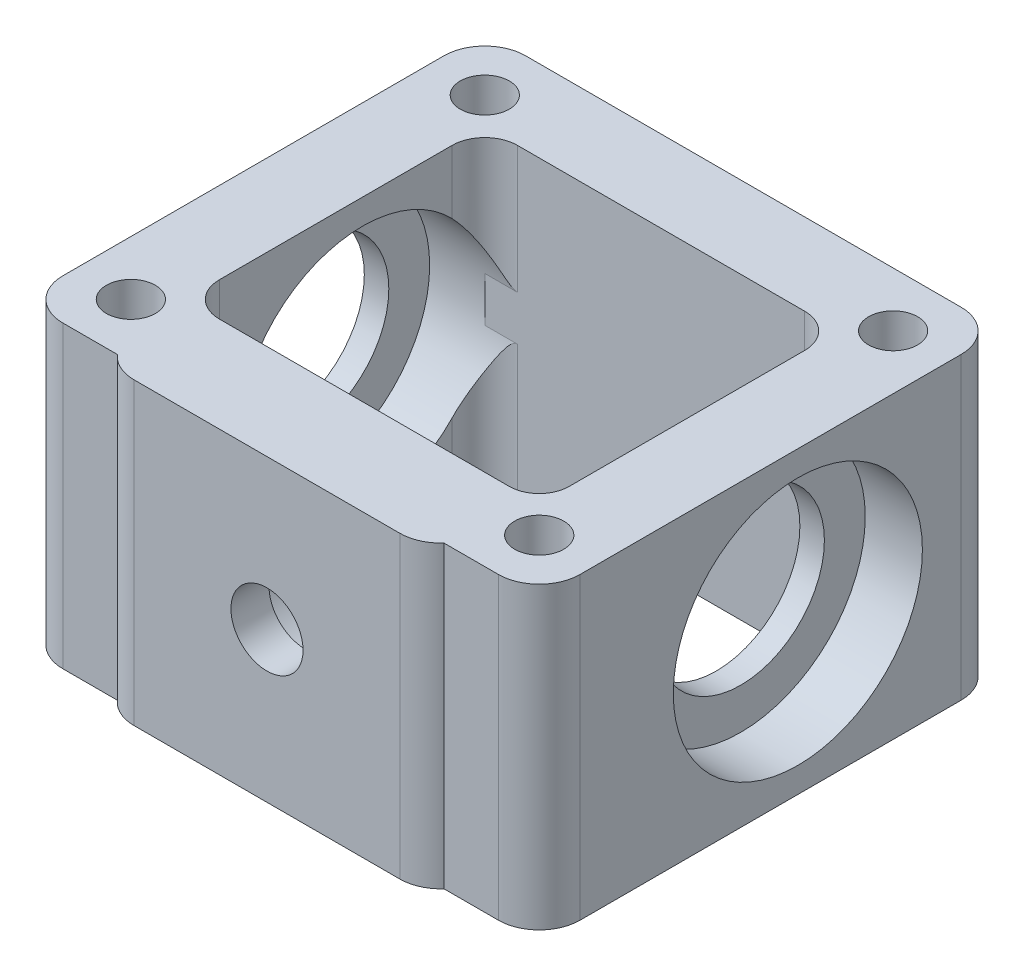
SolidWorks part; units mm, degrees
ref_plane "Front" through (0, 0, 0) normal (0, 0, 1) x (1, 0, 0)
ref_plane "Top" through (0, 0, 0) normal (0, 1, 0) x (1, 0, 0)
ref_plane "Right" through (0, 0, 0) normal (1, 0, 0) x (0, 0, -1)
sketch "Sketch3" plane through (0, 0, 0) normal (0, 1, 0) x (1, 0, 0)
  line L0 (6, -6) -> (32, -6)
  line L1 (0, 0) -> (38, 0)
  line L2 (0, 0) -> (0, -34)
  line L3 (0, -34) -> (38, -34)
  line L4 (38, 0) -> (38, -34)
  line L5 (32, -6) -> (32, -28)
  line L6 (6, -28) -> (32, -28)
  line L7 (6, -6) -> (6, -28)
  dimension "D1" = 38
  dimension "D2" = 34
  dimension "D3" = 6
extrude "Boss-Extrude1" add sketch "Sketch3" along normal blind 22
sketch "Sketch4" plane through (0, 0, 34) normal (0, 0, 1) x (1, 0, 0)
  line L0 (0, 0) -> (38, 0) construction
  line L1 (31, 0) -> (7, 0)
  line L2 (31, 0) -> (31, 22)
  line L3 (31, 22) -> (7, 22)
  line L4 (7, 0) -> (7, 22)
  line L5 (0, 22) -> (38, 22) construction
  dimension "D1" = 24
  dimension "D2" = 7
extrude "Boss-Extrude2" add sketch "Sketch4" along normal blind 1
sketch "Sketch5" plane through (0, 0, 35) normal (0, 0, 1) x (1, 0, 0)
  line L0 (31, 0) -> (31, 22) construction
  line L1 (7, 0) -> (31, 0) construction
  circle A0 centre (19, 11) radius 2.65
  dimension "D3" = 5.3
  dimension "D2" = 11
extrude "Cut-Extrude1" cut sketch "Sketch5" against normal blind 12
sketch "Sketch7" plane through (0, 0, 28) normal (0, 0, -1) x (-1, 0, 0)
  circle A0 centre (-19, 11) radius 5.65
  dimension "D1" = 11.3
extrude "Cut-Extrude3" cut sketch "Sketch7" against normal blind 4.2
sketch "Sketch8" plane through (38, 0, 0) normal (1, 0, 0) x (0, 0, -1)
  line L0 (0, 22) -> (0, 0) construction
  line L1 (-34, 0) -> (0, 0) construction
  circle A0 centre (-15, 11) radius 6.15
  dimension "D1" = 12.3
  dimension "D2" = 15
  dimension "D3" = 11
extrude "Cut-Extrude4" cut sketch "Sketch8" against normal through all
sketch "Sketch9" plane through (6, 0, 0) normal (1, 0, 0) x (0, 0, -1)
  circle A0 centre (-15, 11) radius 9.15
  dimension "D1" = 18.3
extrude "Cut-Extrude5" cut sketch "Sketch9" against normal blind 4.2
sketch "Sketch10" plane through (38, 0, 0) normal (1, 0, 0) x (0, 0, -1)
  circle A0 centre (-15, 11) radius 9.15
  dimension "D1" = 18.3
extrude "Cut-Extrude6" cut sketch "Sketch10" against normal blind 4.2
sketch "Sketch15" plane through (0, 0, 0) normal (0, -1, 0) x (-1, 0, 0)
  line L0 (0, 0) -> (0, -34) construction
  line L1 (0, -34) -> (-7, -34) construction
  circle A0 centre (-4, -30) radius 1.8
  circle A1 centre (-34, -30) radius 1.8
  circle A2 centre (-34, -4) radius 1.8
  circle A3 centre (-4, -4) radius 1.8
  dimension "D1" = 3.6
  dimension "D2" = 4
  dimension "D3" = 4
  dimension "D4" = 2
  dimension "D5" = 2
extrude "Cut-Extrude7" cut sketch "Sketch15" against normal through all
fillet "Fillet1" radius 3 6 edges at (38, 11, 0) (7, 11, 35) (0, 11, 34) (0, 11, 0) (31, 11, 35) (38, 11, 34)
fillet "Fillet3" radius 2.5 2 edges at (32, 11, 6) (6, 11, 28)
fillet "Fillet4" radius 2.2 1 edges at (32, 11, 28)
fillet "Fillet5" radius 2.4 2 edges at (6, 4.675, 6) (6, 17.325, 6)
equation "\"滑动-垂直孔\" = 0.6"
equation "\"滑动-水平孔\"= 0.3"
equation "\"松动-垂直孔\" = 0.3"
equation "\"松动-水平孔\"= 0.1"
equation "\"正常-垂直孔\" = 0.15"
equation "\"正常-水平孔\"= 0"
equation "\"紧缩-垂直孔\"= 0"
equation "\"紧缩-水平孔\"= - 0.1"
equation "\"D1@Sketch15\"=\"滑动-垂直孔\"+3"
equation "\"D1@Sketch8\"=\"滑动-水平孔\"+12"
equation "\"D1@Sketch10\"=\"滑动-水平孔\"+18"
equation "\"D1@Sketch9\"=\"滑动-水平孔\"+18"
equation "\"D3@Sketch5\"=\"滑动-水平孔\"+5"
equation "\"D1@Sketch7\"=\"滑动-水平孔\"+11mm"
